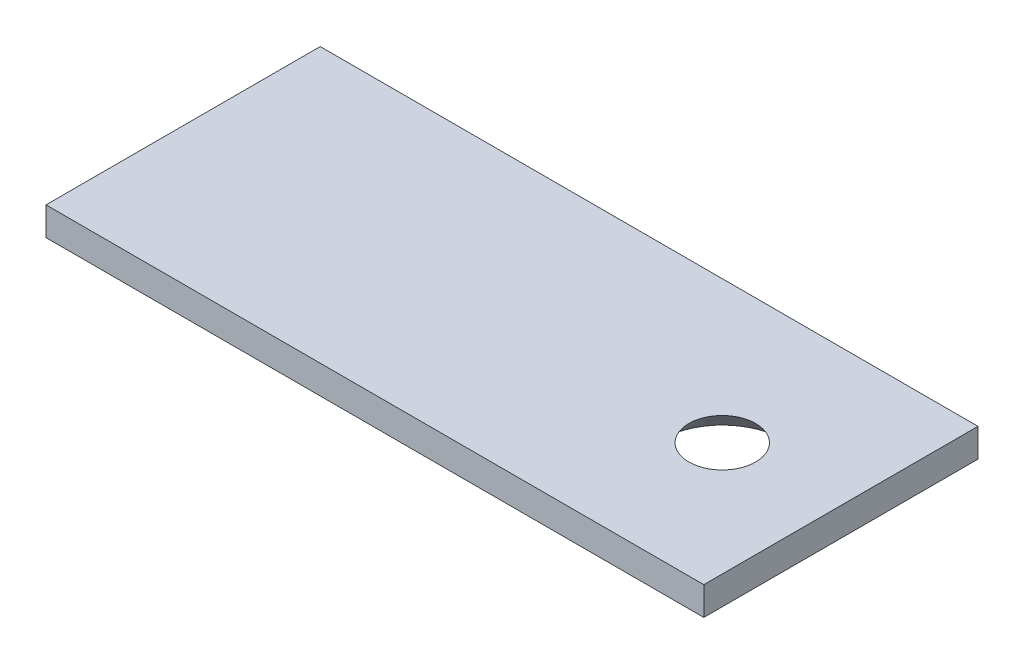
SolidWorks part; units mm, degrees
material "1060 Сплав"
ref_plane "Front" through (0, 0, 0) normal (0, 0, 1) x (1, 0, 0)
ref_plane "Top" through (0, 0, 0) normal (0, 1, 0) x (1, 0, 0)
ref_plane "Right" through (0, 0, 0) normal (1, 0, 0) x (0, 0, -1)
sketch "Эскиз1" plane through (0, 0, 0) normal (1, 0, 0) x (0, 0, -1)
  line L1 (0, 0) -> (19.3, 0)
  line L2 (0, 0) -> (0, 2)
  line L3 (0, 2) -> (19.3, 2)
  line L4 (19.3, 0) -> (19.3, 2)
  dimension "D1" = 2
  dimension "D2" = 19.3
base flange "Базовая кромка1" sketch "Эскиз1" thickness 46.3 reverse thickness direction no parameters "D1"=0.8
sketch "Эскиз6" plane through (0, 2, 0) normal (0, 1, 0) x (1, 0, 0)
  line L0 (0, 19.3) -> (0, 0) construction
  line L1 (-46.3, 0) -> (0, 0) construction
  circle A0 centre (-8, 10) radius 2.3
  dimension "D1" = 4.6
  dimension "D2" = 8
  dimension "D3" = 10
extrude "Вырез-Вытянуть1" [suppressed] cut sketch "Эскиз6" against normal through all
chamfer "Фаска1" [suppressed] distance 2.05 angle 45
sketch "Эскиз7" plane through (0, 2, 0) normal (0, 1, 0) x (1, 0, 0)
  line L0 (0, 19.3) -> (0, 0) construction
  line L1 (-46.3, 19.3) -> (0, 19.3) construction
  circle A0 centre (-8, 9.3) radius 2.3
  dimension "D1" = 4.6
  dimension "D2" = 8
  dimension "D3" = 10
extrude "Вырез-Вытянуть2" cut sketch "Эскиз7" against normal through all normal cut yes
chamfer "Фаска2" distance 2.05 angle 45 1 edges at (-8, 0, -7)
sketch "Сгиб-Линии1" [suppressed] plane through (0, 0, 0) normal (0, 1, 0) x (1, 0, 0)
sketch "Граничная рамка1" [suppressed] plane through (0, 0, 0) normal (0, 1, 0) x (1, 0, 0)
sheet metal parameters "Листовой металл1" thickness 46.3 parameters "D1"=0.8
flat pattern "Развертка1" [suppressed]
sketch "Сгиб-Линии2" plane through (0, 0, 0) normal (0, 1, 0) x (1, 0, 0)
sketch3d "Граничная рамка2" [suppressed]
  line L0 (19.3, 0, 0) -> (0, 0, 0) construction
  line L1 (19.3, 2, 0) -> (0, 2, 0) construction
  line L2 (19.3, 0, 0) -> (19.3, 2, 0) construction
  line L3 (0, 0, 0) -> (0, 2, 0) construction
sheet metal parameters "Листовой металл2" thickness 46.3 parameters "D1"=0.8
flat pattern "Развертка1"
sketch "Сгиб-Линии2" plane through (0, 0, 0) normal (0, 1, 0) x (1, 0, 0)
sketch3d "Граничная рамка2" [suppressed]
  line L0 (19.3, 0, 0) -> (0, 0, 0) construction
  line L1 (19.3, 2, 0) -> (0, 2, 0) construction
  line L2 (19.3, 0, 0) -> (19.3, 2, 0) construction
  line L3 (0, 0, 0) -> (0, 2, 0) construction
sheet metal parameters "Листовой металл3" thickness 46.3 parameters "D1"=0.8
flat pattern "Развертка1"
sketch "Сгиб-Линии2" plane through (0, 0, 0) normal (0, 1, 0) x (1, 0, 0)
sketch3d "Граничная рамка2" [suppressed]
  line L0 (19.3, 0, 0) -> (0, 0, 0) construction
  line L1 (19.3, 2, 0) -> (0, 2, 0) construction
  line L2 (19.3, 0, 0) -> (19.3, 2, 0) construction
  line L3 (0, 0, 0) -> (0, 2, 0) construction
